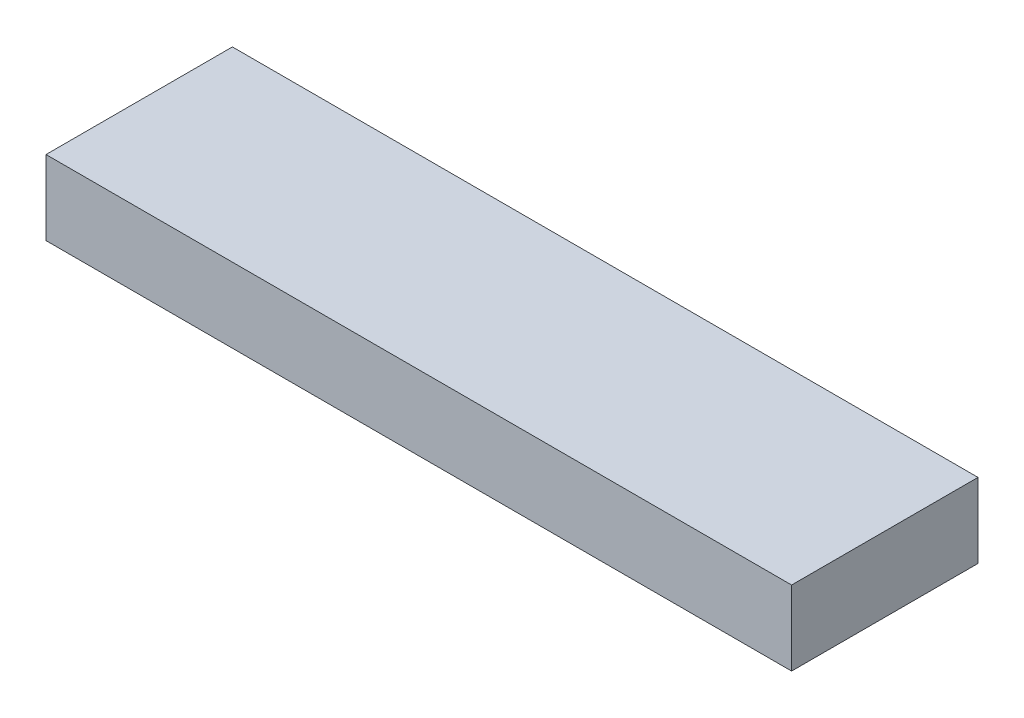
SolidWorks part; units mm, degrees
ref_plane "Front Plane" through (0, 0, 0) normal (0, 0, 1) x (1, 0, 0)
ref_plane "Top Plane" through (0, 0, 0) normal (0, 1, 0) x (1, 0, 0)
ref_plane "Right Plane" through (0, 0, 0) normal (1, 0, 0) x (0, 0, -1)
sketch "Sketch1" plane through (0, 0, 0) normal (0, 1, 0) x (1, 0, 0)
  line L1 (-10, -2.5) -> (10, -2.5)
  line L2 (-10, -2.5) -> (-10, 2.5)
  line L3 (-10, 2.5) -> (10, 2.5)
  line L4 (10, -2.5) -> (10, 2.5)
  line L5 (-10, -2.5) -> (10, 2.5) construction
  line L6 (-10, 2.5) -> (10, -2.5) construction
  line L7 (-9, -1.5) -> (9, -1.5)
  line L8 (-9, -1.5) -> (-9, 1.5)
  line L9 (-9, 1.5) -> (9, 1.5)
  line L10 (9, -1.5) -> (9, 1.5)
  line L11 (-9, -1.5) -> (9, 1.5) construction
  line L12 (-9, 1.5) -> (9, -1.5) construction
  circle A0 centre (-7.5, 0) radius 1.5
  circle A1 centre (-2.5, 0) radius 1.5
  circle A2 centre (2.5, 0) radius 1.5
  circle A3 centre (7.5, 0) radius 1.5
  circle A4 centre (0, 0) radius 1
  circle A5 centre (5, 0) radius 1
  circle A6 centre (-5, 0) radius 1
  point P0 (0, 0)
  point P6 (0, 0)
  dimension "D1" = 5
  dimension "D2" = 20
  dimension "D3" = 1
  dimension "D4" = 1
  dimension "D5" = 4
  dimension "D6" = 2
  dimension "D7" = 2
extrude "Boss-Extrude1" add sketch "Sketch1" along normal blind 1 contours L2 L3 L4 L1
extrude "Boss-Extrude2" add sketch "Sketch1<3>" against normal blind 1 contours L1 L4 L3 L2 L10 L7 L8 L9 | A6 | A4 | A5 region at (-9.7938, 0, 0) region at (-5, 0, 0) region at (0, 0, 0) region at (5, 0, 0)
sketch "Sketch1<3>" plane through (0, 0, 0) normal (0, 1, 0) x (1, 0, 0) same geometry as "Sketch1"
